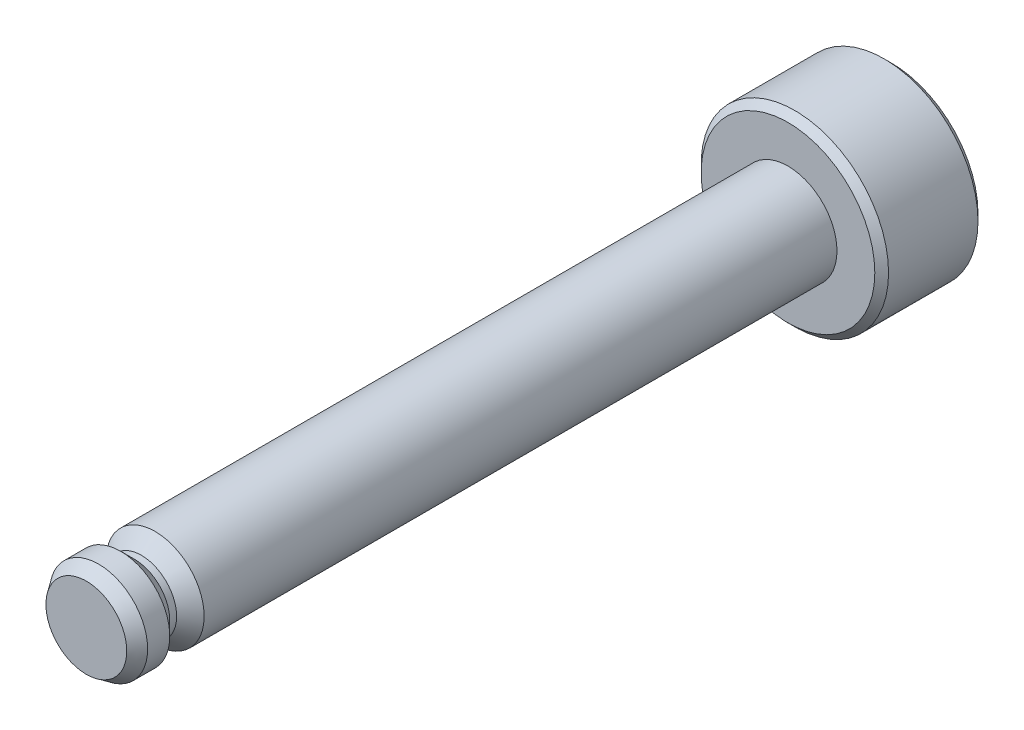
SolidWorks part; units mm, degrees
ref_plane "Front" through (0, 0, 0) normal (0, 0, 1) x (1, 0, 0)
ref_plane "Top" through (0, 0, 0) normal (0, 1, 0) x (1, 0, 0)
ref_plane "Right" through (0, 0, 0) normal (1, 0, 0) x (0, 0, -1)
sketch "Sketch2" plane through (0, 0, 0) normal (0, 0, 1) x (1, 0, 0)
  circle A0 centre (0, 0) radius 1.425
  dimension "D1" = 2.85
extrude "Shaft" add sketch "Sketch2" along normal blind 20.4
sketch "Sketch5" plane through (0, 0, 0) normal (0, 0, 1) x (1, 0, 0)
  circle A0 centre (0, 0) radius 2.725
  dimension "D1" = 5.45
extrude "Head" add sketch "Sketch5" against normal blind 3
sketch "Sketch4" plane through (0, 0, 0) normal (1, 0, 0) x (0, 0, -1)
  line L0 (0, 0) -> (-18.9, 0) construction
  line L1 (-18.9, 0) -> (-18.9, 4.3666) construction
  line L2 (-19.4, 1.425) -> (-18.4, 1.425)
  line L3 (0, 1.425) -> (-20.4, 1.425) construction
  line L6 (-18.4, 1.425) -> (-18.8, 1.025)
  line L7 (-18.8, 1.025) -> (-19, 1.025)
  line L8 (-19, 1.025) -> (-19.4, 1.425)
  line L10 (-18.9, 50) -> (-18.9, -50) construction
  dimension "D2" = 1
  dimension "D3" = 45
  dimension "D4" = 0.4
revolve "e-Clip Notch Short" cut sketch "Sketch4" angle 360 about L0
chamfer "Chamfer1" distance 0.25 angle 55 1 edges at (1.425, 0, 20.4) first distance on face at (1.425, 0, 20.4)
chamfer "Deburs" distance 0.2 angle 45 2 edges at (2.725, 0, 0) (2.725, 0, -3)
sketch "Sketch6" [suppressed] plane through (0, 0, 0) normal (1, 0, 0) x (0, 0, -1)
  line L0 (0, 0) -> (-27.9, 0) construction
  line L1 (-27.9, 0) -> (-27.9, 1.025) construction
  line L2 (0, 1.425) -> (-29.643, 1.425) construction
  line L3 (-28.4, 1.425) -> (-27.4, 1.425)
  line L4 (-27.4, 1.425) -> (-27.8, 1.025)
  line L5 (-27.8, 1.025) -> (-28, 1.025)
  line L6 (-28, 1.025) -> (-28.4, 1.425)
  line L7 (-27.9, 1.025) -> (-27.9, 1.425) construction
  line L8 (-19.4, 1.425) -> (-18.4, 1.425) construction
  line L9 (-19, 1.025) -> (-19.4, 1.425) construction
  line L10 (-27.9, 50) -> (-27.9, -50) construction
revolve "e-Clip Notch Long" [suppressed] cut sketch "Sketch6" angle 360 about L0
equation "\"D1@Sketch2\"=\"Plastic Hardware OD@Box Assy.Assembly\""
equation "\"D1@Sketch5\"=\"Hardware Head Countersink Diameter@Box Assy.Assembly\"-.3mm"
equation "\"D1@Head\"=\"Countersink Depth@Box Assy.Assembly\""
